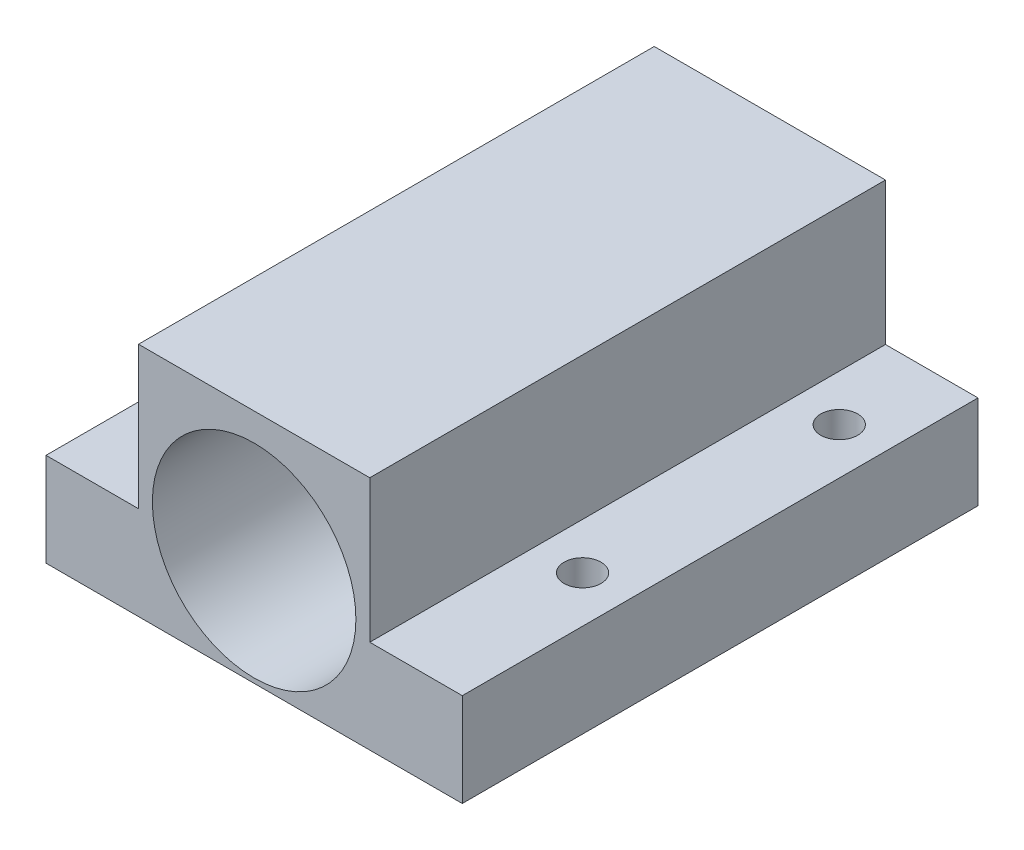
SolidWorks part; units mm, degrees
material "ABS"
ref_plane "Front Plane" through (0, 0, 0) normal (0, 0, 1) x (1, 0, 0)
ref_plane "Top Plane" through (0, 0, 0) normal (0, 1, 0) x (1, 0, 0)
ref_plane "Right Plane" through (0, 0, 0) normal (1, 0, 0) x (0, 0, -1)
sketch "Sketch1" plane through (0, 0, 0) normal (0, 0, 1) x (1, 0, 0)
  line L0 (-65.4098, -16.7) -> (184.5902, -16.7) construction
  line L1 (-12.5, 8.8) -> (12.5, 8.8)
  line L2 (-12.5, 8.8) -> (-12.5, -16.7)
  line L3 (-12.5, -16.7) -> (12.5, -16.7)
  line L4 (12.5, 8.8) -> (12.5, -16.7)
  line L5 (-12.5, 8.8) -> (12.5, -16.7) construction
  line L6 (-12.5, -16.7) -> (12.5, 8.8) construction
  line L7 (12.5, -16.7) -> (22.5, -16.7)
  line L8 (12.5, -16.7) -> (12.5, -6.6)
  line L9 (12.5, -6.6) -> (22.5, -6.6)
  line L10 (22.5, -16.7) -> (22.5, -6.6)
  line L11 (12.5, -16.7) -> (22.5, -6.6) construction
  line L12 (12.5, -6.6) -> (22.5, -16.7) construction
  line L13 (-12.5, -16.7) -> (-22.5, -16.7)
  line L14 (-12.5, -16.7) -> (-12.5, -6.6)
  line L15 (-12.5, -6.6) -> (-22.5, -6.6)
  line L16 (-22.5, -16.7) -> (-22.5, -6.6)
  line L17 (-12.5, -16.7) -> (-22.5, -6.6) construction
  line L18 (-12.5, -6.6) -> (-22.5, -16.7) construction
  circle A0 centre (0, -5.2) radius 4.1
  circle A1 centre (0, -5.2) radius 11
  point P8 (0, -5.2)
  point P14 (17.5, -11.65)
  point P16 (-17.5, -11.65)
  dimension "D4" = 8.2
  dimension "D5" = 22
  dimension "D11" = 14
  dimension "D2" = 0
  dimension "D3" = 25
  dimension "D6" = 10
  dimension "D8" = 10
  dimension "D9" = 10.1
  dimension "D10" = 12.5
  dimension "D12" = 11.5
  dimension "D13" = 5.2
extrude "Boss-Extrude1" add sketch "Sketch1" along normal up to surface (55.75 mm away) contours L4 L1 L2 L3 A1 | L16 L13 L2 L15 | L7 L10 L9 L4 region at (0, 8.4429, 0) region at (-17.5, -11.65, 0) region at (17.5, -11.65, 0)
sketch "Sketch2" plane through (0, -6.6, 0) normal (0, 1, 0) x (1, 0, 0)
  line L0 (-22.5, 0) -> (-12.5, -55.75)
  line L1 (-12.5, -55.75) -> (-22.5, -55.75)
  line L2 (-22.5, -55.75) -> (-12.5, 0)
  line L3 (12.5, 0) -> (22.5, -55.75)
  line L4 (22.5, -55.75) -> (22.5, 0)
  line L5 (22.5, 0) -> (12.5, -55.75)
  circle A0 centre (-17.5, -10) radius 2
  circle A1 centre (17.5, -10) radius 2
  circle A2 centre (17.5, -10) radius 2 construction
  circle A3 centre (-17.5, -10) radius 2 construction
  circle A4 centre (-17.5, -37.75) radius 2
  circle A5 centre (17.5, -37.75) radius 2
  circle A6 centre (17.5, -37.75) radius 2 construction
  circle A7 centre (-17.5, -37.75) radius 2 construction
  dimension "D1" = 4
  dimension "D2" = 4
extrude "Cut-Extrude1" cut sketch "Sketch2" against normal through all contours A0 | A4 | A1 | A5
